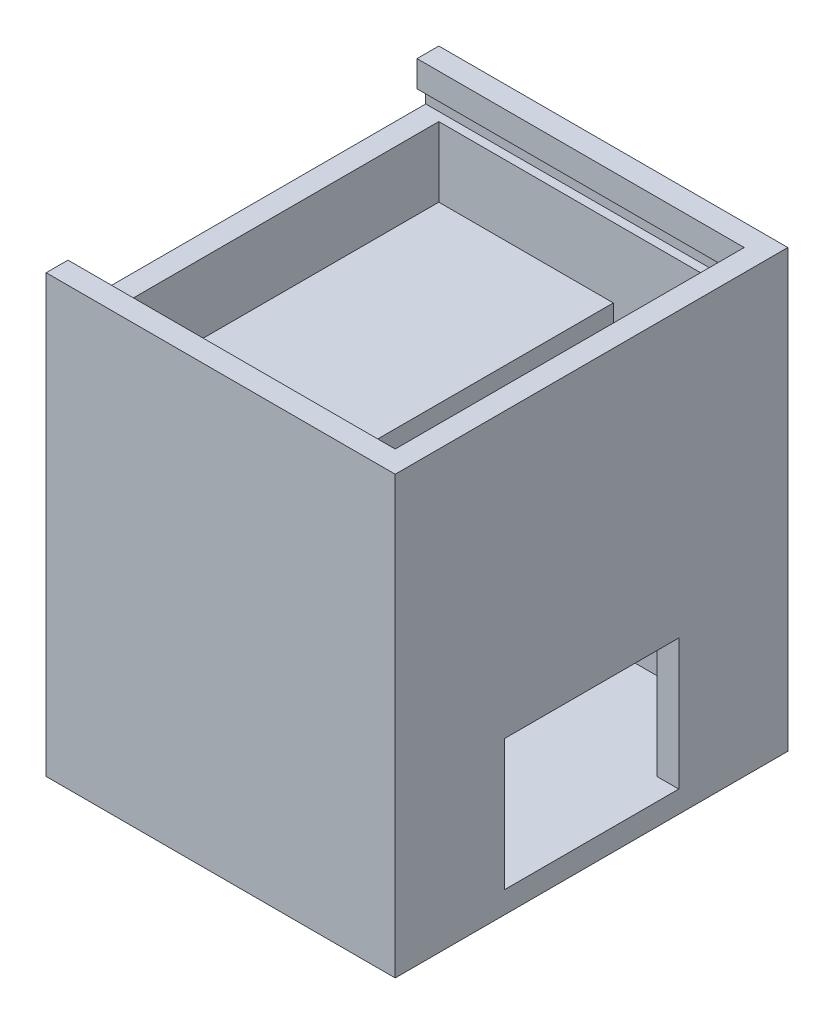
SolidWorks part; units mm, degrees
ref_plane "Front Plane" through (0, 0, 0) normal (0, 0, 1) x (1, 0, 0)
ref_plane "Top Plane" through (0, 0, 0) normal (0, 1, 0) x (1, 0, 0)
ref_plane "Right Plane" through (0, 0, 0) normal (1, 0, 0) x (0, 0, -1)
sketch "Sketch1" plane through (0, 0, 0) normal (0, 1, 0) x (1, 0, 0)
  line L1 (-34.8887, 14.0503) -> (5.1113, 14.0503)
  line L2 (-34.8887, 14.0503) -> (-34.8887, -30.9497)
  line L3 (-34.8887, -30.9497) -> (5.1113, -30.9497)
  line L4 (5.1113, 14.0503) -> (5.1113, -30.9497)
extrude "Boss-Extrude1" add sketch "Sketch1" along normal blind 50
shell "Shell1" thickness 2.5 removed face at (-14.8887, 50, 8.4497)
sketch "Sketch3" plane through (-32.3887, 0, 0) normal (1, 0, 0) x (0, 0, -1)
  line L0 (-28.4497, 50) -> (-28.4497, 2.5) construction
  line L1 (11.5503, 2.5) -> (-28.4497, 2.5)
  line L2 (11.5503, 2.5) -> (11.5503, 37)
  line L3 (11.5503, 37) -> (-28.4497, 37)
  line L4 (-28.4497, 2.5) -> (-28.4497, 37)
extrude "Boss-Extrude2" add sketch "Sketch3" along normal blind 20
sketch "Sketch8" plane through (2.6113, 0, 0) normal (-1, 0, 0) x (0, 0, 1)
  line L3 (-1.5503, 2.5) -> (18.4497, 2.5)
  line L4 (-1.5503, 2.5) -> (-1.5503, 17.5)
  line L5 (-1.5503, 17.5) -> (18.4497, 17.5)
  line L6 (18.4497, 2.5) -> (18.4497, 17.5)
  line L7 (-1.5503, 2.5) -> (18.4497, 17.5) construction
  line L8 (-1.5503, 17.5) -> (18.4497, 2.5) construction
  line L10 (28.4497, 2.5) -> (-11.5503, 2.5) construction
  point P4 (8.4497, 10)
extrude "Cut-Extrude1" cut sketch "Sketch8" against normal blind 2.5
sketch "Sketch11" plane through (-32.3887, 0, 0) normal (1, 0, 0) x (0, 0, -1)
  line L0 (-28.4497, 50) -> (-28.4497, 37) construction
  line L1 (11.5503, 50) -> (-28.4497, 50)
  line L2 (11.5503, 50) -> (11.5503, 45)
  line L3 (11.5503, 45) -> (-28.4497, 45)
  line L4 (-28.4497, 50) -> (-28.4497, 45)
extrude "Cut-Extrude2" cut sketch "Sketch11" against normal blind 2.5
sketch "Sketch12" plane through (0, 0, -11.5503) normal (0, 0, 1) x (1, 0, 0)
  line L0 (2.6113, 50) -> (2.6113, 2.5) construction
  line L1 (-34.8887, 45) -> (2.6113, 45)
  line L2 (-34.8887, 45) -> (-34.8887, 47)
  line L3 (-34.8887, 47) -> (2.6113, 47)
  line L4 (2.6113, 45) -> (2.6113, 47)
sketch "Sketch13" plane through (0, 0, 28.4497) normal (0, 0, -1) x (-1, 0, 0)
  line L0 (-2.6113, 50) -> (-2.6113, 2.5) construction
  line L1 (34.8887, 45) -> (-2.6113, 45)
  line L2 (34.8887, 45) -> (34.8887, 47)
  line L3 (34.8887, 47) -> (-2.6113, 47)
  line L4 (-2.6113, 45) -> (-2.6113, 47)
extrude "Cut-Extrude3" cut sketch "Sketch12" against normal blind 1
extrude "Cut-Extrude4" cut sketch "Sketch13" against normal blind 1
